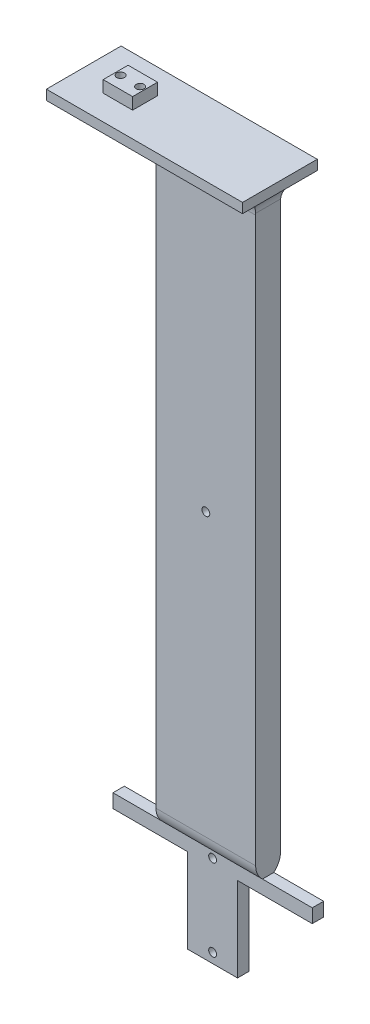
SolidWorks part; units mm, degrees
ref_plane "Front Plane" through (0, 0, 0) normal (0, 0, 1) x (1, 0, 0)
ref_plane "Top Plane" through (0, 0, 0) normal (0, 1, 0) x (1, 0, 0)
ref_plane "Right Plane" through (0, 0, 0) normal (1, 0, 0) x (0, 0, -1)
sketch "Sketch1" plane through (0, 0, 0) normal (0, 1, 0) x (1, 0, 0)
  line L1 (-50, 19.05) -> (50, 19.05)
  line L2 (-50, 19.05) -> (-50, -19.05)
  line L3 (-50, -19.05) -> (50, -19.05)
  line L4 (50, 19.05) -> (50, -19.05)
  line L5 (-50, 19.05) -> (50, -19.05) construction
  line L6 (-50, -19.05) -> (50, 19.05) construction
  point P0 (0, 0)
  dimension "D1" = 100
  dimension "D2" = 38.1
extrude "Boss-Extrude1" add sketch "Sketch1" along normal blind 5
sketch "Sketch2" plane through (0, 5, 0) normal (0, 1, 0) x (1, 0, 0)
  line L1 (-33.7366, 6.35) -> (-18.7366, 6.35)
  line L2 (-33.7366, 6.35) -> (-33.7366, -6.35)
  line L3 (-33.7366, -6.35) -> (-18.7366, -6.35)
  line L4 (-18.7366, 6.35) -> (-18.7366, -6.35)
  line L5 (-33.7366, 6.35) -> (-18.7366, -6.35) construction
  line L6 (-33.7366, -6.35) -> (-18.7366, 6.35) construction
  point P0 (-26.2366, 0)
  dimension "D1" = 12.7
  dimension "D2" = 15
extrude "Boss-Extrude2" add sketch "Sketch2" along normal blind 6
sketch "Sketch3" plane through (0, 11, 0) normal (0, 1, 0) x (1, 0, 0)
  line L0 (-33.7366, 6.35) -> (-33.7366, -6.35) construction
  circle A0 centre (-21.2366, 0) radius 2
  circle A1 centre (-31.2366, 0) radius 2
  dimension "D1" = 4
  dimension "D2" = 4
  dimension "D3" = 10
  dimension "D4" = 2.5
sketch "Sketch11" plane through (0, 11, 0) normal (0, 1, 0) x (1, 0, 0)
  point P0 (-31.2366, 0)
  point P3 (-21.2366, 0)
hole_wizard "Tap Drill for M4x0.7 Tap1" positions "Sketch11" profile "Sketch10" hole size "M4x0.7" standard "ANSI Metric" end condition through all
sketch "Sketch10" plane through (-31.2366, 11, 0) normal (1, 0, 0) x (0, 0, 1)
  line L0 (0, 0) -> (0, 11)
  line L1 (0, 11) -> (1.65, 11)
  line L2 (1.65, 11) -> (1.65, 0)
  line L5 (1.65, 0) -> (0, 0)
  line L11 (0, -6.35) -> (0, 107.95) construction
  dimension "Thru Hole Dia." = 3.3
  dimension "Thru Hole Depth" = 11
extrude "Cut-Extrude1" cut sketch "Sketch3" against normal through all
sketch "Sketch12" plane through (0, 0, 0) normal (0, -1, 0) x (1, 0, 0)
  circle A0 centre (-31.2366, 0) radius 3.5
  circle A1 centre (-21.2366, 0) radius 3.5
  dimension "D1" = 7
  dimension "D2" = 7
extrude "Cut-Extrude2" cut sketch "Sketch12" against normal blind 3
sketch "Sketch13" plane through (0, 0, 0) normal (0, -1, 0) x (1, 0, 0)
  line L0 (50, 19.05) -> (50, -19.05) construction
  line L1 (-6.8, 6.35) -> (44, 6.35)
  line L2 (-6.8, 6.35) -> (-6.8, -6.35)
  line L3 (-6.8, -6.35) -> (44, -6.35)
  line L4 (44, 6.35) -> (44, -6.35)
  line L5 (-6.8, 6.35) -> (44, -6.35) construction
  line L6 (-6.8, -6.35) -> (44, 6.35) construction
  point P0 (18.6, 0)
  point P7 (50, 0)
  dimension "D1" = 50.8
  dimension "D2" = 12.7
  dimension "D3" = 6
extrude "Boss-Extrude3" add sketch "Sketch13" along normal blind 304.8
sketch "Sketch14" plane through (0, -304.8, 0) normal (0, -1, 0) x (1, 0, 0)
  line L0 (18.6, 6.35) -> (18.6, -6.35) construction
  line L1 (44, 6.35) -> (-6.8, 6.35) construction
  line L2 (-6.8, -6.35) -> (44, -6.35) construction
  line L3 (-6.8, 0) -> (44, 0) construction
  line L4 (-6.8, 6.35) -> (-6.8, -6.35) construction
  line L5 (44, -6.35) -> (44, 6.35) construction
  line L7 (-32.2, 2.9) -> (69.4, 2.9)
  line L8 (-32.2, 2.9) -> (-32.2, -2.9)
  line L9 (-32.2, -2.9) -> (69.4, -2.9)
  line L10 (69.4, 2.9) -> (69.4, -2.9)
  line L11 (-32.2, 2.9) -> (69.4, -2.9) construction
  line L12 (-32.2, -2.9) -> (69.4, 2.9) construction
  point P12 (18.6, 0)
  dimension "D1" = 101.6
  dimension "D2" = 5.8
extrude "Boss-Extrude4" add sketch "Sketch14" along normal blind 7
fillet "Fillet1" radius 10 1 edges at (18.6, -304.8, -6.35)
fillet "Fillet2" radius 10 1 edges at (18.6, -304.8, 6.35)
fillet "Fillet3" radius 10 4 edges at (44, 0, 0) (18.6, 0, -6.35) (-6.8, 0, 0) (18.6, 0, 6.35)
sketch "Sketch15" plane through (0, 0, -2.9) normal (0, 0, -1) x (-1, 0, 0)
  line L0 (-18.6, -304.8) -> (-18.6, -311.8) construction
  line L1 (6.8, -304.8) -> (-44, -304.8) construction
  line L2 (32.2, -311.8) -> (-69.4, -311.8) construction
  line L3 (-69.4, -308.3) -> (32.2, -308.3) construction
  line L4 (-69.4, -311.8) -> (-69.4, -304.8) construction
  line L5 (32.2, -311.8) -> (32.2, -304.8) construction
  circle A0 centre (-18.6, -308.3) radius 2
  dimension "D1" = 4
extrude "Cut-Extrude3" cut sketch "Sketch15" against normal through all
sketch "Sketch16" plane through (0, -311.8, 0) normal (0, -1, 0) x (1, 0, 0)
  line L0 (18.6, 2.9) -> (18.6, -2.9) construction
  line L1 (44, 2.9) -> (-6.8, 2.9) construction
  line L2 (-6.8, -2.9) -> (44, -2.9) construction
  line L3 (-32.2, 0) -> (69.4, 0) construction
  line L4 (-32.2, 2.9) -> (-32.2, -2.9) construction
  line L5 (69.4, -2.9) -> (69.4, 2.9) construction
  line L6 (-32.2, -2.9) -> (69.4, -2.9) construction
  line L7 (5.9, 2.9) -> (31.3, 2.9)
  line L8 (5.9, 2.9) -> (5.9, -2.9)
  line L9 (5.9, -2.9) -> (31.3, -2.9)
  line L10 (31.3, 2.9) -> (31.3, -2.9)
  line L11 (5.9, 2.9) -> (31.3, -2.9) construction
  line L12 (5.9, -2.9) -> (31.3, 2.9) construction
  point P12 (18.6, 0)
  dimension "D1" = 25.4
extrude "Boss-Extrude5" add sketch "Sketch16" along normal blind 43.038
sketch "Sketch17" plane through (0, 0, -2.9) normal (0, 0, -1) x (-1, 0, 0)
  line L0 (-18.6, -304.8) -> (-18.6, -354.838) construction
  line L1 (6.8, -304.8) -> (-44, -304.8) construction
  line L2 (-5.9, -354.838) -> (-31.3, -354.838) construction
  line L3 (-31.3, -333.319) -> (-5.9, -333.319) construction
  line L4 (-31.3, -354.838) -> (-31.3, -311.8) construction
  line L5 (-5.9, -354.838) -> (-5.9, -311.8) construction
  circle A0 centre (-18.6, -349.838) radius 2
  dimension "D1" = 4
  dimension "D2" = 5
extrude "Cut-Extrude4" cut sketch "Sketch17" against normal through all
sketch "Sketch18" plane through (0, 0, 6.35) normal (0, 0, 1) x (1, 0, 0)
  line L0 (44, -153.6219) -> (-6.8, -153.6219) construction
  line L1 (44, -297.2437) -> (44, -10) construction
  line L2 (-6.8, -297.2437) -> (-6.8, -10) construction
  circle A0 centre (18.6, -153.6219) radius 2
  dimension "D1" = 4
extrude "Cut-Extrude5" cut sketch "Sketch18" against normal through all
